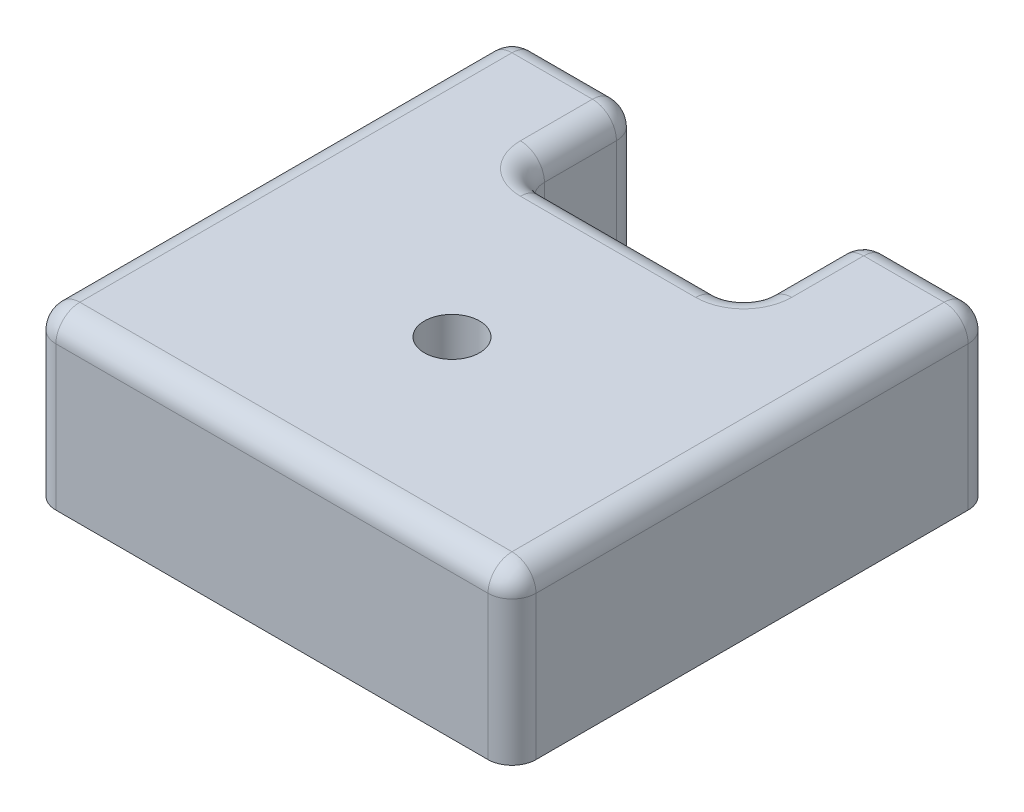
SolidWorks part; units mm, degrees
ref_plane "Front Plane" through (0, 0, 0) normal (0, 0, 1) x (1, 0, 0)
ref_plane "Top Plane" through (0, 0, 0) normal (0, 1, 0) x (1, 0, 0)
ref_plane "Right Plane" through (0, 0, 0) normal (1, 0, 0) x (0, 0, -1)
sketch "Sketch2" plane through (0, 0, 0) normal (0, 1, 0) x (1, 0, 0)
  line L0 (14.65, 20) -> (20, 20)
  line L1 (0, 0) -> (20, 0)
  line L2 (0, 0) -> (0, 20)
  line L3 (0, 20) -> (5.35, 20)
  line L4 (20, 0) -> (20, 20)
  line L6 (5.35, 20) -> (5.35, 15)
  line L7 (5.35, 15) -> (14.65, 15)
  line L8 (14.65, 20) -> (14.65, 15)
  dimension "D1" = 20
  dimension "D2" = 9.3
  dimension "D3" = 20
  dimension "D4" = 5
  dimension "D5" = 5.35
extrude "Boss-Extrude1" add sketch "Sketch2" along normal blind 7 contours L4 L0 L8 L7 L6 L3 L2 L1
fillet "Fillet1" radius 1 16 edges at (0, 7, -10) (2.675, 7, -20) (5.35, 7, -17.5) (10, 7, -15) (14.65, 7, -17.5) (17.325, 7, -20) (20, 7, -10) (10, 7, 0) (0, 3.5, 0) (20, 3.5, 0) (20, 3.5, -20) (0, 3.5, -20) (14.65, 3.5, -20) (14.65, 3.5, -15) (5.35, 3.5, -15) (5.35, 3.5, -20)
sketch "Sketch3" plane through (0, 7, 0) normal (0, 1, 0) x (1, 0, 0)
  line L0 (10, 1) -> (10, 14) construction
  line L1 (1, 1) -> (19, 1) construction
  line L2 (13.65, 14) -> (6.35, 14) construction
  circle A0 centre (10, 7.5) radius 1.15
  dimension "D1" = 2.3
extrude "Cut-Extrude1" cut sketch "Sketch3" against normal through all
